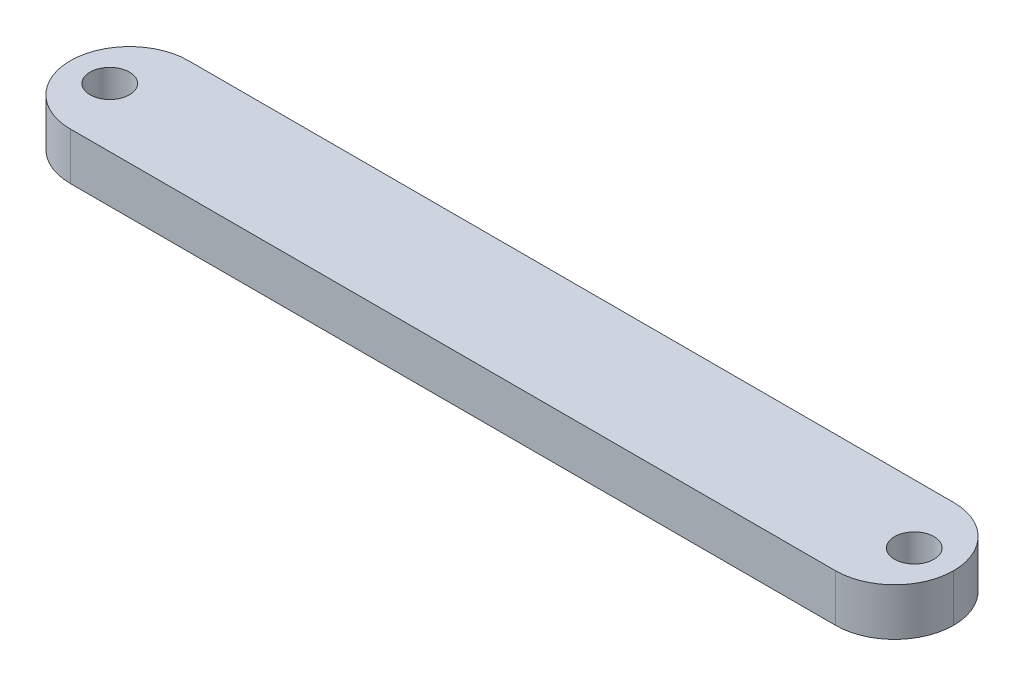
SolidWorks part; units mm, degrees
ref_plane "Front Plane" through (0, 0, 0) normal (0, 0, 1) x (1, 0, 0)
ref_plane "Top Plane" through (0, 0, 0) normal (0, 1, 0) x (1, 0, 0)
ref_plane "Right Plane" through (0, 0, 0) normal (1, 0, 0) x (0, 0, -1)
sketch "Sketch1" plane through (0, 0, 0) normal (0, 1, 0) x (1, 0, 0)
  line L1 (0, 0) -> (112.08, 0)
  line L2 (0, 0) -> (0, 15)
  line L3 (0, 15) -> (112.08, 15)
  line L4 (112.08, 0) -> (112.08, 15)
  circle A0 centre (5, 7.5) radius 2.5
  circle A1 centre (107.08, 7.5) radius 2.5
  dimension "D2" = 5
  dimension "D3" = 5
  dimension "D6" = 5
  dimension "D1" = 15
  dimension "D4" = 5
  dimension "D5" = 7.5
  dimension "D7" = 7.5
  dimension "D8" = 102.08
extrude "Boss-Extrude1" add sketch "Sketch1" along normal blind 6
fillet "Fillet1" radius 7.5 4 edges at (112.08, 3, 0) (112.08, 3, -15) (0, 3, -15) (0, 3, 0)
